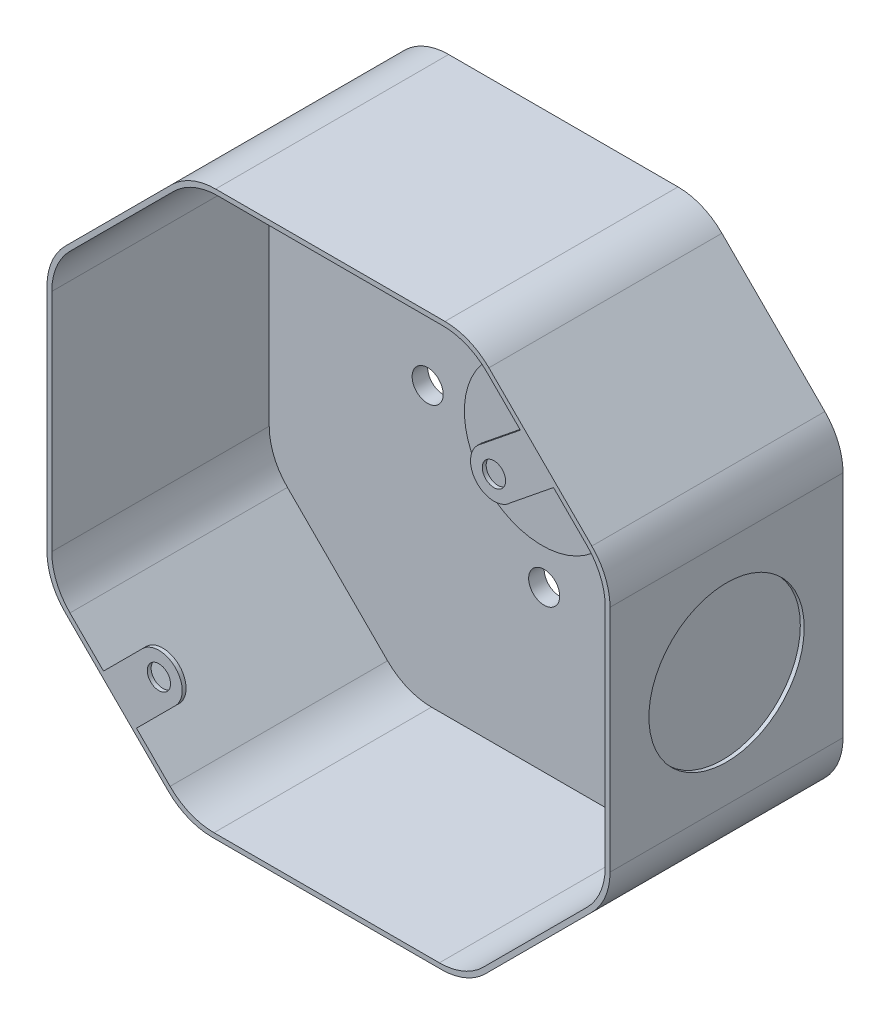
SolidWorks part; units mm, degrees
material "Cast Alloy Steel"
ref_plane "Front Plane" through (0, 0, 0) normal (0, 0, 1) x (1, 0, 0)
ref_plane "Top Plane" through (0, 0, 0) normal (0, 1, 0) x (1, 0, 0)
ref_plane "Right Plane" through (0, 0, 0) normal (1, 0, 0) x (0, 0, -1)
ref_axis "X-axis" through (-88.99, 0, 0) along (1, 0, 0)
ref_axis "Y-axis" through (0, 55, 0) along (0, -1, 0)
ref_axis "Z-axis" through (0, 0, -88.99) along (0, 0, 1)
sketch "Sketch3" plane through (0, 0, 0) normal (0, 0, 1) x (1, 0, 0)
  line L0 (-22.9598, 0) -> (22.9598, 0)
  line L4 (22.9598, 0) -> (46.3324, 23.3726)
  line L5 (46.3324, 23.3726) -> (46.3324, 69.2941)
  line L6 (46.3324, 69.2941) -> (23.5515, 92.075)
  line L7 (23.5515, 92.075) -> (-22.3682, 92.075)
  line L8 (-22.9598, 0) -> (-45.7407, 22.7809)
  line L9 (-45.7407, 22.7809) -> (-45.7407, 68.7024)
  line L10 (-45.7407, 68.7024) -> (-22.3682, 92.075)
  line L11 (-45.7407, 68.7024) -> (116.3369, 68.7024) construction
  line L12 (-45.7407, 22.7809) -> (116.3369, 22.7809) construction
  point P4 (0, 0)
  dimension "D1" = 92.075
  dimension "D2" = 92.075
  dimension "D3" = 135
extrude "Boss-Extrude1" add sketch "Sketch3" along normal blind 38.1
sketch "Sketch4" plane through (0, 0, 38.1) normal (0, 0, 1) x (1, 0, 0)
  line L16 (23.2253, 91.2876) -> (-22.042, 91.2876)
  line L17 (-22.042, 91.2876) -> (-44.9533, 68.3763)
  line L18 (-44.9533, 68.3763) -> (-44.9533, 23.1071)
  line L19 (-44.9533, 23.1071) -> (-22.6337, 0.7874)
  line L20 (-22.6337, 0.7874) -> (22.6337, 0.7874)
  line L21 (22.6337, 0.7874) -> (45.545, 23.6987)
  line L22 (45.545, 23.6987) -> (45.545, 68.9679)
  line L23 (45.545, 68.9679) -> (23.2253, 91.2876)
  line L24 (23.2253, 91.2876) -> (-22.042, 91.2876)
  line L25 (-22.042, 91.2876) -> (-44.9533, 68.3763)
  line L26 (-44.9533, 68.3763) -> (-44.9533, 23.1071)
  line L27 (-44.9533, 23.1071) -> (-22.6337, 0.7874)
  line L28 (-22.6337, 0.7874) -> (22.6337, 0.7874)
  line L29 (22.6337, 0.7874) -> (45.545, 23.6987)
  line L30 (45.545, 23.6987) -> (45.545, 68.9679)
  line L31 (45.545, 68.9679) -> (23.2253, 91.2876)
  dimension "D1" = 0.7874
extrude "Cut-Extrude1" cut sketch "Sketch4" against normal blind 35.56
sketch "Sketch5" plane through (0, 0, 2.54) normal (0, 0, 1) x (1, 0, 0)
  line L0 (-89.707, 46.0248) -> (89.707, 46.0248) construction
  line L1 (0, 100.3044) -> (0, -8.2548) construction
  line L2 (-22.9598, 0) -> (22.9598, 0) construction
  circle A4 centre (0, 46.0248) radius 19.05 construction
  point P3 (0, 46.0248)
  point P7 (0, 46.0248)
  dimension "D1" = 46.0248
sketch "Sketch20" plane through (0, 0, 0) normal (0, 0, 1) x (1, 0, 0)
  line L0 (0, 100.3044) -> (0, -8.2548) construction
  line L1 (-89.707, 46.0248) -> (89.707, 46.0248) construction
  circle A0 centre (0, 65.0748) radius 2.54
  circle A1 centre (0, 46.0248) radius 19.05 construction
  circle A2 centre (19.05, 46.0248) radius 2.54
  circle A3 centre (0, 26.9748) radius 2.54
  circle A4 centre (-19.05, 46.0248) radius 2.54
  dimension "D1" = 5.08
extrude "Cut-Extrude9" cut sketch "Sketch20" against normal through all and the other way through all
sketch "Sketch8" plane through (0, 0, 38.1) normal (0, 0, 1) x (1, 0, 0)
  line L1 (27.3492, 74.4477) -> (34.4211, 80.0918) construction
  line L3 (24.6788, 77.1958) -> (32.2868, 83.3397)
  line L4 (30.0974, 71.7772) -> (37.7054, 77.9211)
  line L9 (46.3324, 69.2941) -> (23.5515, 92.075) construction
  line L10 (32.2868, 83.3397) -> (37.7054, 77.9211)
  arc A0 (24.6788, 77.1958) -> (30.0974, 71.7772) centre (27.3492, 74.4477) ccw
  dimension "D2" = 7.62
  dimension "D1" = 9.779
extrude "Boss-Extrude2" add sketch "Sketch8" against normal blind 0.635
sketch "Sketch9" plane through (0, 0, 38.1) normal (0, 0, 1) x (1, 0, 0)
  circle A0 centre (27.3492, 74.4477) radius 1.905
  dimension "D1" = 3.81
extrude "Cut-Extrude4" cut sketch "Sketch9" against normal blind 3.175
sketch "Sketch11" plane through (0, 0, 38.1) normal (0, 0, 1) x (1, 0, 0)
  line L0 (-41.2651, 4.4757) -> (-27.4355, 18.3052) construction
  line L1 (-45.7407, 22.7809) -> (-22.9598, 0) construction
  line L2 (-37.0443, 14.0845) -> (-30.1295, 20.9993)
  line L3 (-31.6562, 8.6964) -> (-24.7414, 15.6112)
  line L4 (-37.0443, 14.0845) -> (-31.6562, 8.6964)
  arc A1 (-24.7414, 15.6112) -> (-30.1295, 20.9993) centre (-27.4355, 18.3052) ccw
  point P4 (-34.3503, 11.3905)
  dimension "D1" = 9.779
  dimension "D2" = 7.62
extrude "Boss-Extrude3" add sketch "Sketch11" against normal blind 0.635
sketch "Sketch12" plane through (0, 0, 38.1) normal (0, 0, 1) x (1, 0, 0)
  circle A0 centre (-27.4355, 18.3052) radius 1.905
  dimension "D1" = 3.81
extrude "Cut-Extrude5" cut sketch "Sketch12" against normal blind 0.635
sketch "Sketch13" plane through (0, 0, 2.54) normal (0, 0, 1) x (1, 0, 0)
  line L2 (23.5515, 92.075) -> (-22.3682, 92.075) construction
  line L3 (-45.7407, 68.7024) -> (-45.7407, 22.7809) construction
  circle A0 centre (0.2841, 46.0502) radius 12.7
  dimension "D3" = 25.4
  dimension "D1" = 46.0248
  dimension "D2" = 46.0248
extrude "Boss-Extrude4" add sketch "Sketch13" along normal blind 0.635
sketch "Sketch14" plane through (46.3324, 0, 0) normal (1, 0, 0) x (0, 0, -1)
  line L0 (0, 23.3726) -> (0, 69.2941) construction
  line L1 (-38.1, 23.3726) -> (0, 23.3726) construction
  circle A0 centre (-19.05, 46.3342) radius 12.7
  dimension "D1" = 25.4
  dimension "D2" = 19.05
  dimension "D3" = 22.9616
extrude "Cut-Extrude6" cut sketch "Sketch14" against normal blind 0.635
sketch "Sketch15" plane through (-45.7407, 0, 0) normal (-1, 0, 0) x (0, 0, 1)
  line L0 (0, 68.7024) -> (0, 22.7809) construction
  circle A0 centre (19.05, 45.7425) radius 12.7
  dimension "D1" = 25.4
  dimension "D2" = 19.05
extrude "Cut-Extrude7" cut sketch "Sketch15" against normal blind 0.635
sketch "Sketch16" plane through (0, 0, 0) normal (0, -1, 0) x (1, 0, 0)
  line L0 (-22.9598, 0) -> (22.9598, 0) construction
  line L1 (22.9598, 38.1) -> (22.9598, 0) construction
  circle A0 centre (0, 19.05) radius 12.7
  dimension "D1" = 25.4
  dimension "D2" = 19.05
  dimension "D3" = 22.9598
extrude "Cut-Extrude8" cut sketch "Sketch16" against normal blind 0.635
fillet "Fillet1" radius 10.16 8 edges at (46.3324, 23.3726, 19.05) (22.9598, 0, 19.05) (-22.9598, 0, 19.05) (-45.7407, 22.7809, 19.05) (-45.7407, 68.7024, 19.05) (-22.3682, 92.075, 19.05) (23.5515, 92.075, 19.05) (46.3324, 69.2941, 19.05)
fillet "Fillet2" radius 10.16 8 edges at (22.6337, 0.7874, 20.32) (-44.9533, 68.3763, 20.32) (-44.9533, 23.1071, 20.32) (-22.6337, 0.7874, 20.32) (45.545, 23.6987, 20.32) (45.545, 68.9679, 20.32) (23.2253, 91.2876, 20.32) (-22.042, 91.2876, 20.32)
sketch "Sketch19" plane through (0, 0, 0) normal (0, 0, 1) x (1, 0, 0)
  line L0 (0.5917, 91.2876) -> (0, 0) construction
  line L1 (19.0169, 91.2876) -> (-17.8336, 91.2876) construction
  line L2 (-45.7407, 45.7417) -> (46.3324, 46.3333) construction
  line L3 (-45.7407, 64.494) -> (-45.7407, 26.9893) construction
  line L4 (46.3324, 27.581) -> (46.3324, 65.0857) construction
